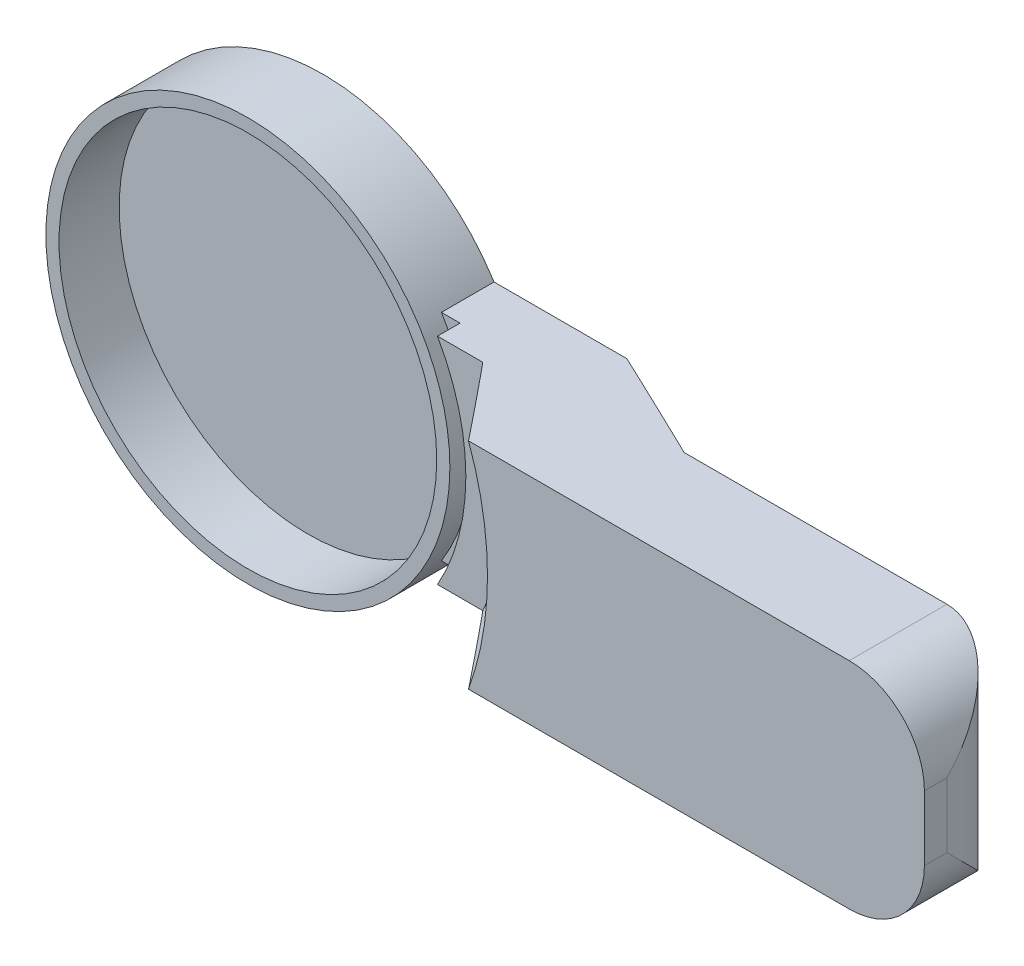
SolidWorks part; units mm, degrees
material "Custom Plastic"
ref_plane "Front Plane" through (0, 0, 0) normal (0, 0, 1) x (1, 0, 0)
ref_plane "Top Plane" through (0, 0, 0) normal (0, 1, 0) x (1, 0, 0)
ref_plane "Right Plane" through (0, 0, 0) normal (1, 0, 0) x (0, 0, -1)
sketch "Sketch1" plane through (0, 0, 0) normal (0, 0, 1) x (1, 0, 0)
  circle A0 centre (0, 0) radius 26.875
  dimension "D1" = 53.75
extrude "Boss-Extrude1" add sketch "Sketch1" along normal blind 2
sketch "Sketch2" plane through (0, 0, 2) normal (0, 0, 1) x (1, 0, 0)
  circle A0 centre (0, 0) radius 26.875
  circle A1 centre (0, 0) radius 25.125
  dimension "D1" = 50.25
  dimension "D2" = 53.75
extrude "Boss-Extrude2" add sketch "Sketch2" along normal blind 8
ref_plane "Plane1" through (0, 0, 20) normal (0, 0, 1) x (1, 0, 0)
sketch "Sketch3" plane through (0, 0, 20) normal (0, 0, 1) x (1, 0, 0)
  line L0 (100, 14.31) -> (22.7484, 14.31)
  line L5 (100, -14.31) -> (22.7484, -14.31)
  line L6 (100, 14.31) -> (100, -14.31)
  circle A3 centre (0, 0) radius 26.875 construction
  arc A4 (22.7484, 14.31) -> (22.7484, -14.31) centre (0, 0) cw
  dimension "D1" = 100
extrude "Boss-Extrude3" add sketch "Sketch3" against normal blind 13 contours L0 A4 L5 L6
chamfer "Chamfer1" distance 20 distance2 15 1 edges at (26.875, 0, 20) first distance on face at (24.8117, 0, 15)
chamfer "Chamfer2" distance 30 distance2 15 1 edges at (26.875, 0, 7) first distance on face at (62.4059, 0, 7)
sketch "Sketch8" plane through (0, 0, 10) normal (0, 0, 1) x (1, 0, 0)
  circle A0 centre (0, 0) radius 25.125
  circle A1 centre (0, 0) radius 26.875
  circle A2 centre (0, 0) radius 29
  dimension "D1" = 53.75
  dimension "D2" = 50.25
  dimension "D3" = 58
extrude "Cut-Extrude4" cut sketch "Sketch8" against normal blind 3 contours A2 A1 region at (-28.1798, 0, 10)
fillet "Fillet1" radius 10 3 edges at (100, 0, 7) (100, -14.31, 13.5) (100, 14.31, 13.5)
